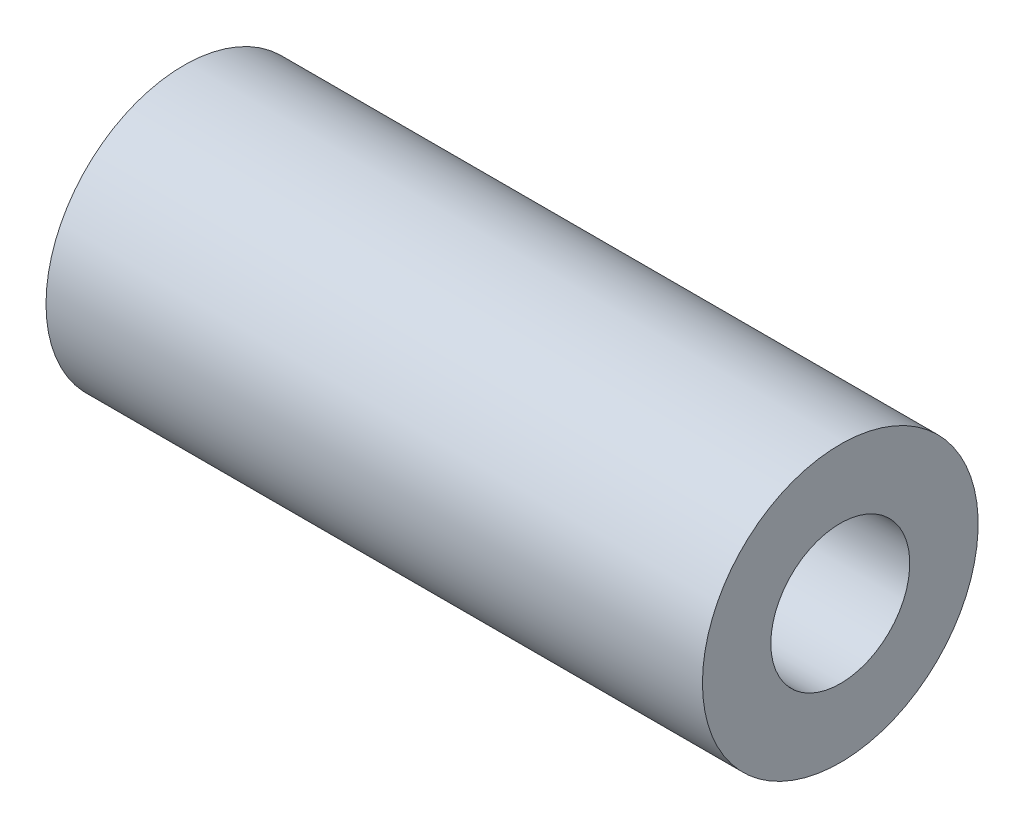
SolidWorks part; units mm, degrees
ref_plane "Front Plane" through (0, 0, 0) normal (0, 0, 1) x (1, 0, 0)
ref_plane "Top Plane" through (0, 0, 0) normal (0, 1, 0) x (1, 0, 0)
ref_plane "Right Plane" through (0, 0, 0) normal (1, 0, 0) x (0, 0, -1)
sketch "Union_T6 Sketch" plane through (0, 0, 0) normal (0, 0, 1) x (1, 0, 0)
  line L0 (-1000, 0) -> (1000, 0) construction
  line L1 (-22.5, 0) -> (-22.5, 9.45)
  line L2 (-22.5, 9.45) -> (-0.5, 9.45)
  line L3 (-0.5, 9.45) -> (0.5, 9.45)
  line L4 (0.5, 9.45) -> (22.5, 9.45)
  line L5 (22.5, 9.45) -> (22.5, 0)
  line L6 (22.5, 0) -> (-22.5, 0)
revolve "Union_T6" add sketch "Union_T6 Sketch" angle 360 about L0
ref_axis "Engine Axis" through (24.75, 0, 0) along (-1, 0, 0)
sketch "Socket 1 Sketch" plane through (0, 0, 0) normal (0, 0, 1) x (1, 0, 0)
  line L0 (-1000, 0) -> (1000, 0) construction
  line L1 (-23.5, 0) -> (-23.5, 4.7625)
  line L2 (-23.5, 4.7625) -> (-5.7, 4.7625)
  line L3 (-5.7, 4.7625) -> (-5.7, 0)
  line L4 (-5.7, 0) -> (-23.5, 0)
revolve "Socket 1" cut sketch "Socket 1 Sketch" angle 360 about L0
sketch "Socket 2 Sketch" plane through (0, 0, 0) normal (0, 0, 1) x (1, 0, 0)
  line L0 (-1000, 0) -> (1000, 0) construction
  line L1 (5.7, 0) -> (5.7, 4.7625)
  line L2 (5.7, 4.7625) -> (23.5, 4.7625)
  line L3 (23.5, 4.7625) -> (23.5, 0)
  line L4 (23.5, 0) -> (5.7, 0)
revolve "Socket 2" cut sketch "Socket 2 Sketch" angle 360 about L0
